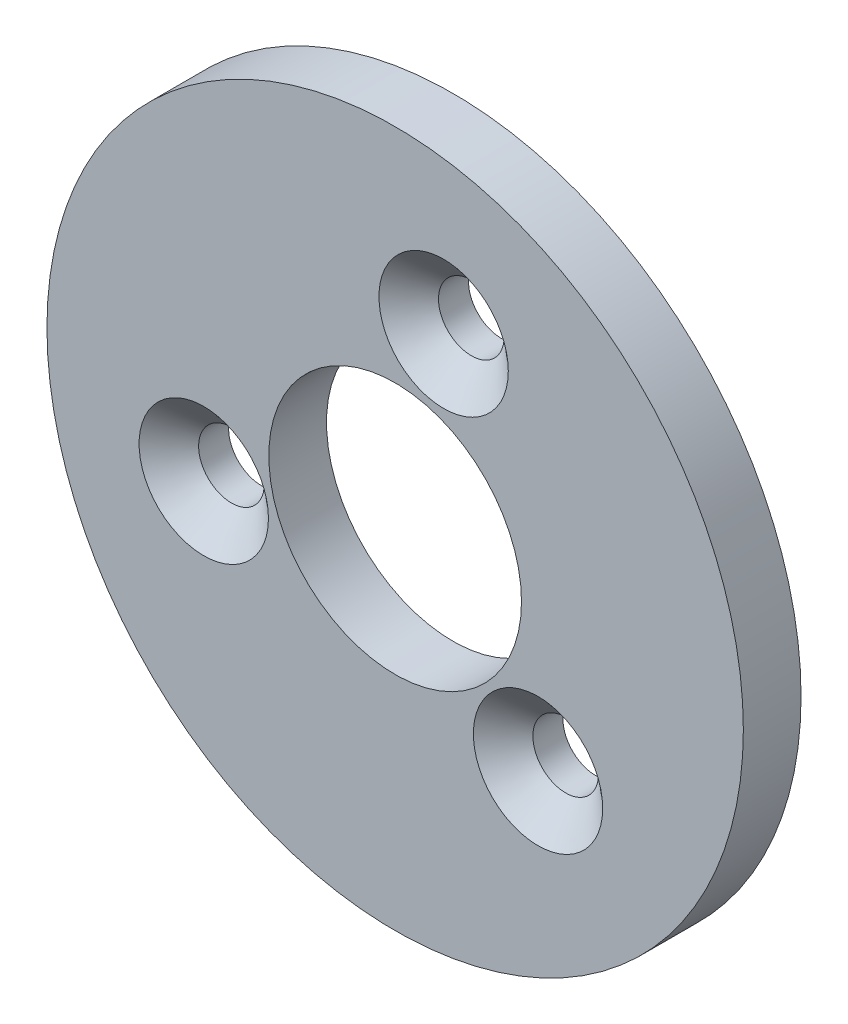
SolidWorks part; units mm, degrees
ref_plane "Front Plane" through (0, 0, 0) normal (0, 0, 1) x (1, 0, 0)
ref_plane "Top Plane" through (0, 0, 0) normal (0, 1, 0) x (1, 0, 0)
ref_plane "Right Plane" through (0, 0, 0) normal (1, 0, 0) x (0, 0, -1)
sketch "Sketch1" plane through (0, 0, 0) normal (0, 0, 1) x (1, 0, 0)
  circle A0 centre (0, 0) radius 17.5
  dimension "D1" = 35
extrude "Boss-Extrude1" add sketch "Sketch1" along normal blind 2.9
sketch "Sketch2" plane through (0, 0, 2.9) normal (0, 0, 1) x (1, 0, 0)
  circle A3 centre (-9.6176, -2.7388) radius 1.65
  circle A4 centre (-9.6176, -2.7388) radius 1.65
  circle A5 centre (7.1807, -6.9597) radius 1.65
  circle A6 centre (7.1807, -6.9597) radius 1.65
  circle A7 centre (2.437, 9.6985) radius 1.65
  circle A8 centre (2.437, 9.6985) radius 1.65
  dimension "D2" = 0
  dimension "D3" = 0
  dimension "D4" = 0
extrude "Cut-Extrude1" cut sketch "Sketch2" against normal through all
chamfer "Chamfer1" distance 1.6 angle 41 3 edges at (-7.9676, -2.7388, 2.9) (4.087, 9.6985, 2.9) (8.8307, -6.9597, 2.9) first distance on face at (8.8307, -6.9597, 2.9)
sketch "Sketch3" plane through (0, 0, 2.9) normal (0, 0, 1) x (1, 0, 0)
  circle A1 centre (0, 0) radius 6.35
  circle A2 centre (0, 0) radius 6.35
  dimension "D1" = 0
extrude "Cut-Extrude2" cut sketch "Sketch3" against normal through all
equation "\"smallPulleyTeeth\"= 15"
equation "\"largePulleyTeeth\"= 30"
equation "\"eighthThick\"= 2.9mm"
equation "\"sixteenthThick\" = 1.7mm"
equation "\"quarterThick\"=5.6mm"
equation "\"OD\" = 150mm"
equation "\"puckAngle\" = 60.5deg"
equation "\"puckDiam\" = 76.5mm"
equation "\"axlePress\" = 5.8mm"
equation "\"press\" = 0.2mm"
equation "\"wheelClear\" = 0.3mm"
equation "\"10-32clear\" = 4.5mm"
equation "\"D1@Boss-Extrude1\"=\"eighthThick\""
equation "\"D1@Chamfer1\"=(6.5-\"6-32clear\")/2"
equation "\"6-32clear\" = 3.3mm"
equation "\"8-32clear\" = 4.0mm"
